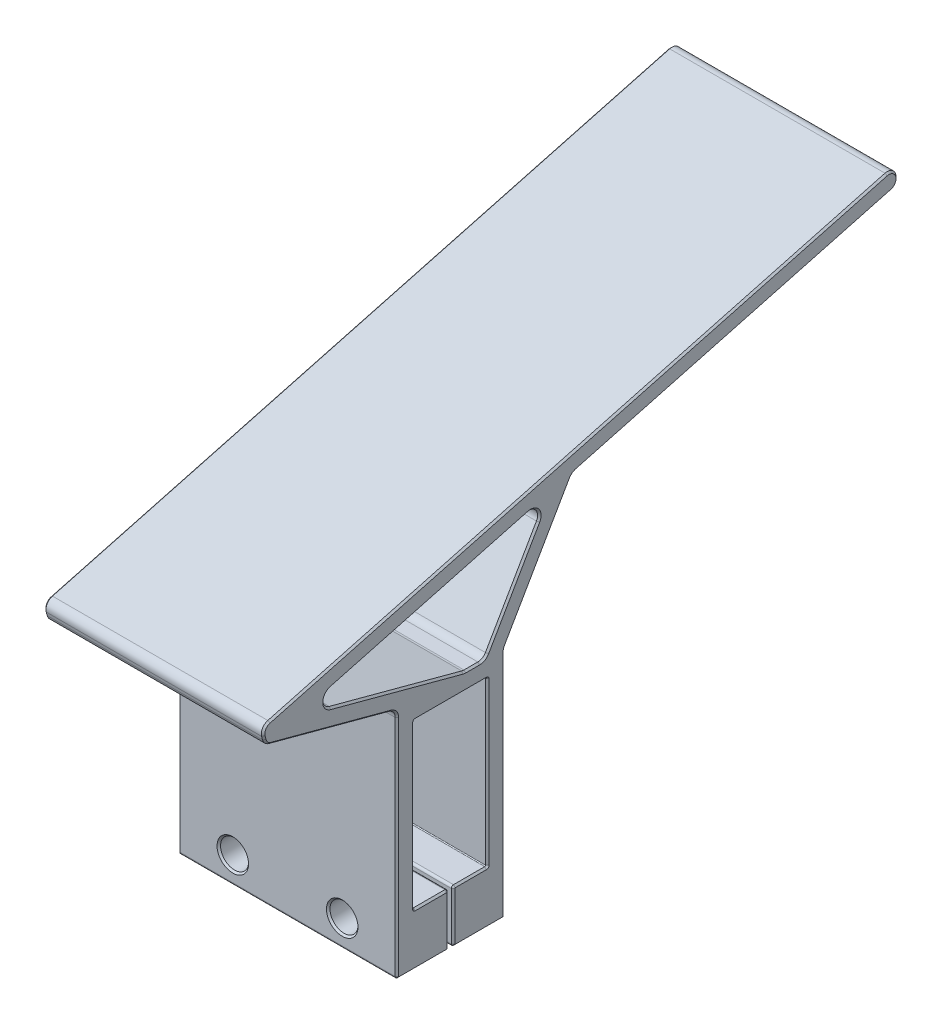
SolidWorks part; units mm, degrees
ref_plane "Front Plane" through (0, 0, 0) normal (1, 0, 0) x (0, 1, 0)
ref_plane "Top Plane" through (0, 0, 0) normal (0, 0, 1) x (0, 1, 0)
ref_plane "Right Plane" through (0, 0, 0) normal (0, 1, 0) x (-1, 0, 0)
sketch "Sketch1" plane through (0, 0, 0) normal (1, 0, 0) x (0, 1, 0)
  line L0 (4, -4) -> (30.8361, -19.4939)
  line L1 (0, 0) -> (-37.29, 0)
  line L2 (0, 0) -> (0, 16.66)
  line L3 (0, 16.66) -> (-37.29, 16.66)
  line L4 (-37.29, 0) -> (-37.29, 16.66)
  line L5 (4, -4) -> (-41.29, -4)
  line L6 (4, -4) -> (4, 20.66)
  line L7 (4, 20.66) -> (-41.29, 20.66)
  line L8 (-41.29, -4) -> (-41.29, 20.66)
  line L9 (30.8361, -19.4939) -> (50.8613, -94.2289)
  line L10 (50.8613, -94.2289) -> (54.725, -93.1936)
  line L11 (54.725, -93.1936) -> (15.9022, 51.6953)
  line L12 (15.9022, 51.6953) -> (12.0385, 50.66)
  line L13 (12.0385, 50.66) -> (4, 20.66)
  line L14 (30.8361, -19.4939) -> (12.0385, 50.66) construction
  line L15 (4, 5.2052) -> (14.109, 42.9326)
  line L16 (14.109, 42.9326) -> (29.372, -14.0298)
  line L17 (29.372, -14.0298) -> (4, 0.6188)
  line L18 (-37.29, 8.83) -> (-49.29, 8.83)
  line L19 (-49.29, 8.83) -> (-49.29, 20.66)
  line L20 (-49.29, 20.66) -> (-41.29, 20.66)
  line L21 (-37.29, 7.83) -> (-49.29, 7.83)
  line L22 (-49.29, 7.83) -> (-49.29, -4)
  line L23 (-49.29, -4) -> (-41.29, -4)
  line L24 (-41.29, 8.33) -> (-58.329, 8.33) construction
  dimension "D1" = 4
  dimension "D2" = 150
  dimension "D3" = 4
  dimension "D4" = 4
  dimension "D5" = 4
  dimension "D6" = 4
  dimension "D7" = 16.66
  dimension "D8" = 37.29
  dimension "D9" = 15
  dimension "D10" = 15
  dimension "D11" = 30
  dimension "D12" = 120
  dimension "D13" = 4
  dimension "D14" = 4
  dimension "D16" = 0.5
  dimension "D17" = 0.5
  dimension "D15" = 12
extrude "Boss-Extrude1" add sketch "Sketch1" along normal blind 25 contours L4 L21 L8 L5 L6 L7 L18 L3 L2 L1 | L16 L17 L6 L0 L9 L10 L11 L12 L13 L15 | L20 L19 L18 L8 | L22 L23 L8 L21
sketch "Sketch2" plane through (0, 0, 7.83) normal (0, 0, 1) x (1, 0, 0)
  line L0 (0, -43.29) -> (25, -43.29) construction
  line L4 (0, -37.29) -> (0, -49.29)
  line L5 (0, -49.29) -> (25, -49.29)
  line L6 (25, -49.29) -> (25, -37.29)
  line L7 (25, -37.29) -> (0, -37.29)
  line L8 (0, -37.29) -> (0, -49.29)
  line L9 (0, -49.29) -> (25, -49.29)
  line L10 (25, -49.29) -> (25, -37.29)
  line L11 (25, -37.29) -> (0, -37.29)
  circle A0 centre (12.5, -43.29) radius 3.2
  dimension "D2" = 6.4
  dimension "D1" = 0
extrude "Cut-Extrude1" cut sketch "Sketch2" against normal through all both and the other way through all contours A0 L0 | L0 A0
fillet "Fillet1" radius 2 11 edges at (12.5, 4, -4) (12.5, 30.8361, -19.4939) (12.5, 50.8613, -94.2289) (12.5, 54.725, -93.1936) (12.5, 15.9022, 51.6953) (12.5, 12.0385, 50.66) (12.5, 14.109, 42.9326) (12.5, 29.372, -14.0298) (12.5, 4, 0.6188) (12.5, 4, 5.2052) (12.5, 4, 20.66)
fillet "Fillet2" radius 0.5 6 edges at (12.5, -37.29, 7.83) (12.5, -37.29, 8.83) (12.5, -49.29, 7.83) (12.5, -49.29, 8.83) (12.5, -49.29, -4) (12.5, -49.29, 20.66)
chamfer "Chamfer1" distance 0.4 angle 45 4 edges at (9.3, -43.29, 7.83) (12.5, -40.09, -4) (12.5, -40.09, 20.66) (12.5, -40.09, 8.83)
mirror "Mirror1" about plane through (0, 0, 0) normal (1, 0, 0) of bodies 102
fillet "Fillet3" radius 0.2 4 edges at (0, 0, 0) (0, -37.29, 0) (0, -37.29, 16.66) (0, 0, 16.66)
chamfer "Chamfer2" distance 0.4 angle 45 82 edges at (25, 54.0076, -92.7794) (25, 51.2755, -93.5114) (25, 3.9817, -4.0681) (25, 30.7054, -19.5942) (25, 14.109, 37.2052) (25, 27.408, -11.4702) (25, 4.2679, 0.7735) (25, 4.0171, 5.2029) (25, 3.6829, 21.0733) (25, -43.29, 7.83) (25, -49.29, 14.745) (25, -43.29, 8.83) (25, -37.29, 12.895) (25, -49.29, 1.915) (25, -49.1436, 20.5136) (25, -49.1436, -3.8536) (25, -49.1436, 8.9764) (25, -49.1436, 7.6836) (25, -37.4364, 8.9764) (25, -37.4364, 7.6836) (-25, -43.29, 7.83) (-25, -49.29, 1.915) (-25, 17.2914, -11.6738) (-25, 40.6971, -56.2955) (-25, 35.3136, -20.7492) (-25, 13.5621, 51.0682) (-25, 8.0684, 35.8435) (-25, -23.1623, 20.66) (-25, -37.29, 12.895) (-25, 15.0953, -5.787) (-25, 4, 3.3577) (-25, 8.1227, 20.5912) (-25, 22.0816, 13.1785) (-25, -43.29, 8.83) (-25, -49.29, 14.745) (-25, -22.6629, -4) (-25, 3.9817, -4.0681) (-25, 30.7054, -19.5942) (-25, 54.0076, -92.7794) (-25, 51.2755, -93.5114) (-25, 15.488, 50.9778) (-25, 12.2573, 50.4412) (-25, 14.109, 37.2052) (-25, 27.408, -11.4702) (-25, 4.2679, 0.7735) (-25, 4.0171, 5.2029) (-25, 3.6829, 21.0733) (-25, -37.4364, 7.6836) (-25, -37.4364, 8.9764) (-25, -49.1436, 7.6836) (-25, -49.1436, 8.9764) (-25, -49.1436, -3.8536) (-25, -49.1436, 20.5136) (-25, -18.645, 0) (25, -18.645, 0) (-25, 0, 8.33) (25, 0, 8.33) (-25, -37.29, 3.765) (25, -37.29, 3.765) (-25, -18.645, 16.66) (25, -18.645, 16.66) (-25, -0.0586, 0.0586) (25, -0.0586, 0.0586) (-25, -37.2314, 0.0586) (25, -37.2314, 0.0586) (-25, -37.2314, 16.6014) (25, -37.2314, 16.6014) (-25, -0.0586, 16.6014) (25, -0.0586, 16.6014) (25, 17.2914, -11.6738) (25, -22.6629, -4) (25, 40.6971, -56.2955) (25, 15.0953, -5.787) (25, 4, 3.3577) (25, 8.1227, 20.5912) (25, 22.0816, 13.1785) (25, 35.3136, -20.7492) (25, 13.5621, 51.0682) (25, 8.0684, 35.8435) (25, -23.1623, 20.66) (25, 12.2573, 50.4412) (25, 15.488, 50.9778)
equation "\"D17@Sketch1\"=\"D16@Sketch1\""
